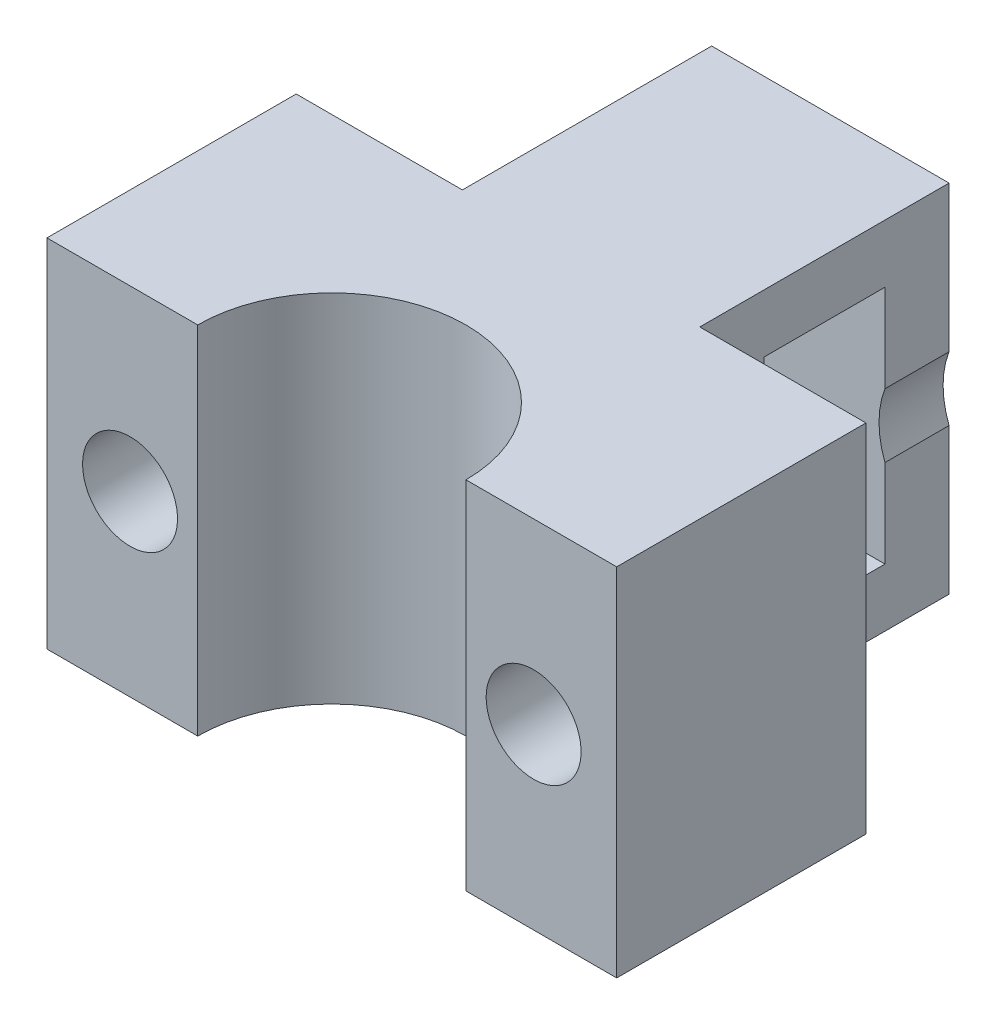
SolidWorks part; units mm, degrees
ref_plane "Спереди" through (0, 0, 0) normal (0, 0, 1) x (1, 0, 0)
ref_plane "Сверху" through (0, 0, 0) normal (0, 1, 0) x (1, 0, 0)
ref_plane "Справа" through (0, 0, 0) normal (1, 0, 0) x (0, 0, -1)
sketch "Эскиз1" plane through (0, 0, 0) normal (0, 1, 0) x (1, 0, 0)
  line L1 (-24, -10) -> (24, -10)
  line L2 (-24, -10) -> (-24, 10)
  line L3 (-24, 10) -> (24, 10)
  line L4 (24, -10) -> (24, 10)
  line L5 (-24, -10) -> (24, 10) construction
  line L6 (-24, 10) -> (24, -10) construction
  point P0 (0, 0)
  dimension "D1" = 48
  dimension "D2" = 20
extrude "Бобышка-Вытянуть1" add sketch "Эскиз1" along normal blind 30
sketch "Эскиз2" plane through (0, 0, 10) normal (0, 0, 1) x (1, 0, 0)
  line L0 (-7, 30) -> (-7, 0)
  line L1 (-24, 30) -> (24, 30) construction
  line L2 (-24, 0) -> (24, 0) construction
  line L3 (-7, 0) -> (7, 0)
  line L4 (7, 0) -> (7, 30)
  line L5 (7, 30) -> (-7, 30)
  dimension "D1" = 17
  dimension "D2" = 14
extrude "Вырез-Вытянуть1" cut sketch "Эскиз2" against normal blind 7
sketch "Эскиз7" plane through (24, 0, 0) normal (1, 0, 0) x (0, 0, -1)
  line L1 (32, 30) -> (32, 0)
  line L2 (32, 0) -> (10, 0)
  line L3 (-10, 0) -> (10, 0)
  line L4 (10, 0) -> (10.066, 0.2736)
  line L5 (10, 30) -> (32, 30)
  line L8 (10, 0) -> (10, 30)
  dimension "D3" = 22
extrude "Бобышка-Вытянуть2" add sketch "Эскиз7" against normal blind 48
sketch "Эскиз8" plane through (24, 0, 0) normal (1, 0, 0) x (0, 0, -1)
  line L0 (11, 0) -> (11, 30)
  line L1 (-10, 30) -> (32, 30) construction
  line L2 (11, 30) -> (32, 30)
  line L3 (11, 0) -> (32, 0)
  line L4 (32, 0) -> (32, 30)
  line L5 (-10, 0) -> (32, 0) construction
  point P16 (11, 0)
extrude "Вырез-Вытянуть2" cut sketch "Эскиз8" against normal blind 14
sketch "Эскиз9" plane through (-24, 0, 0) normal (-1, 0, 0) x (0, 0, 1)
  line L0 (-11, 0) -> (-11, 30)
  line L1 (-32, 30) -> (10, 30) construction
  line L2 (-11, 30) -> (-32, 30)
  line L3 (-32, 0) -> (10, 0) construction
  line L4 (-11, 0) -> (-32, 0)
  line L5 (-32, 0) -> (-32, 30)
  point P15 (-11, 0)
extrude "Вырез-Вытянуть3" cut sketch "Эскиз9" against normal blind 14
sketch "Эскиз11" plane through (-10, 0, 0) normal (-1, 0, 0) x (0, 0, 1)
  line L0 (-32, 30) -> (-11, 0) construction
  line L2 (-32, 0) -> (-11, 0) construction
  line L3 (-16.4, 4.9) -> (-16.4, 25.1)
  line L6 (-16.4, 4.9) -> (-26.6, 4.9)
  line L7 (-16.4, 25.1) -> (-26.6, 25.1)
  line L8 (-26.6, 4.9) -> (-26.6, 25.1)
  line L9 (-16.4, 4.9) -> (-26.6, 25.1) construction
  line L10 (-16.4, 25.1) -> (-26.6, 4.9) construction
  point P7 (-21.5, 15)
  point P8 (-21.5, 15)
  dimension "D1" = 20.2
  dimension "D2" = 10.2
extrude "Вырез-Вытянуть4" cut sketch "Эскиз11" against normal through all
sketch "Эскиз13" plane through (0, 0, -11) normal (0, 0, -1) x (-1, 0, 0)
  line L0 (24, 15) -> (10, 15) construction
  line L1 (24, 0) -> (24, 30) construction
  line L2 (10, 0) -> (10, 30) construction
  circle A0 centre (17, 15) radius 4
extrude "Вырез-Вытянуть5" cut sketch "Эскиз13" against normal through all
sketch "Эскиз14" plane through (0, 0, -11) normal (0, 0, -1) x (-1, 0, 0)
  line L0 (-24, 15) -> (-10, 15) construction
  line L1 (-24, 30) -> (-24, 0) construction
  line L2 (-10, 30) -> (-10, 0) construction
  circle A0 centre (-17, 15) radius 4
extrude "Вырез-Вытянуть6" cut sketch "Эскиз14" against normal through all
fillet "Скругление1" radius 7 2 edges at (-7, 15, 3) (7, 15, 3)
sketch "Эскиз20" plane through (0, 0, -11) normal (0, 0, -1) x (-1, 0, 0)
  circle A0 centre (-17, 15) radius 7.5
  circle A1 centre (17, 15) radius 7.5
  dimension "D1" = 15
extrude "Вырез-Вытянуть8" cut sketch "Эскиз20" along normal through all
sketch "Sketch2" plane through (0, 30, 0) normal (0, 1, 0) x (1, 0, 0)
  line L0 (-7, -10) -> (7, -10) construction
  circle A0 centre (0, -10) radius 11.3
  dimension "D1" = 22.6
extrude "Cut-Extrude1" cut sketch "Sketch2" against normal through all
